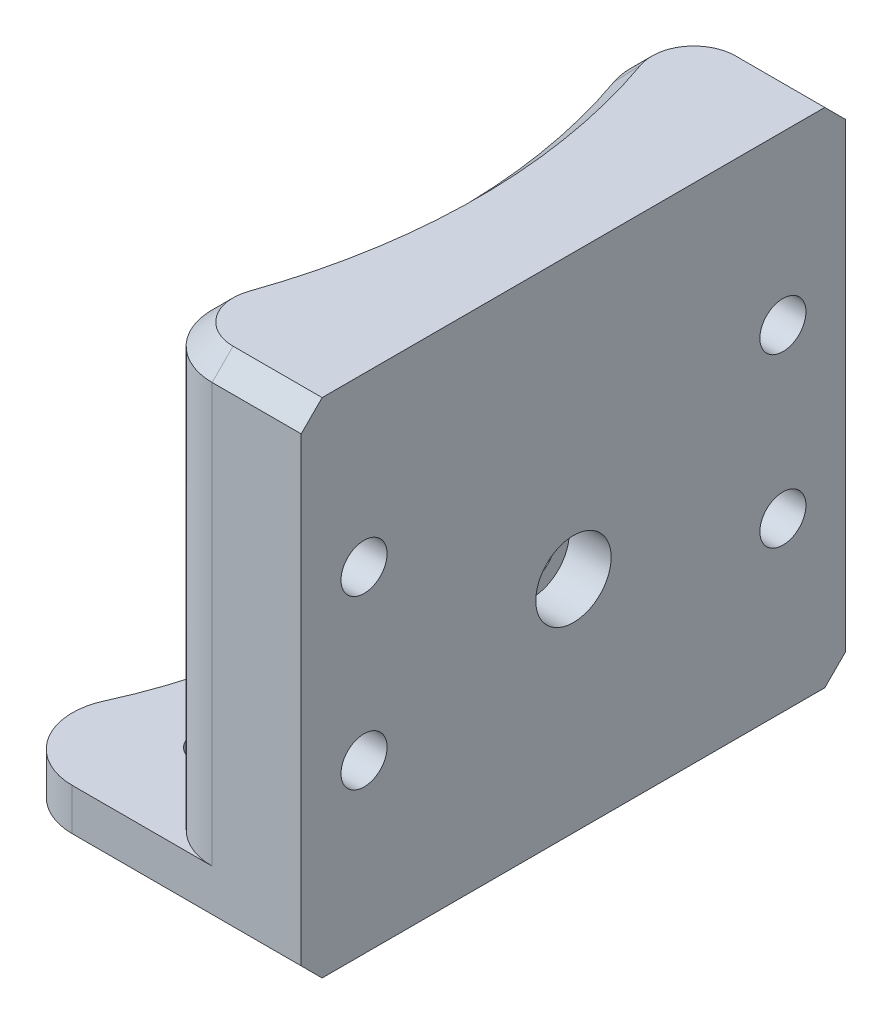
SolidWorks part; units mm, degrees
ref_plane "Спереди" through (0, 0, 0) normal (0, 0, 1) x (1, 0, 0)
ref_plane "Сверху" through (0, 0, 0) normal (0, 1, 0) x (1, 0, 0)
ref_plane "Справа" through (0, 0, 0) normal (1, 0, 0) x (0, 0, -1)
sketch "Эскиз1" plane through (0, 0, 0) normal (0, 1, 0) x (1, 0, 0)
  line L0 (23.6854, 8) -> (23.6854, -8) construction
  line L1 (16.4924, 13) -> (32.75, 13)
  line L2 (16.4924, 13) -> (16.4924, -13) construction
  line L3 (16.4924, -13) -> (32.75, -13)
  line L4 (32.75, 13) -> (32.75, -13)
  circle A0 centre (0, 0) radius 25 construction
  circle A2 centre (0, 0) radius 21
  circle A3 centre (23.6854, 8) radius 1.1
  circle A4 centre (23.6854, -8) radius 1.1
  dimension "D1" = 50
  dimension "D6" = 2.2
  dimension "D7" = 2.2
  dimension "D3" = 26
  dimension "D4" = 32.75
  dimension "D5" = 16
extrude "Бобышка-Вытянуть1" add sketch "Эскиз1" along normal blind 24 contours A2 L3 L4 L1 A4 A3 region at (26.1479, 0, 0)
sketch "Эскиз2" plane through (0, 24, 0) normal (0, 1, 0) x (1, 0, 0)
  circle A0 centre (0, 0) radius 25 construction
  circle A1 centre (0, 0) radius 27.2
  dimension "D1" = 2.2
extrude "Вырез-Вытянуть1" cut sketch "Эскиз2" against normal offset from surface (21 mm away) 3 up to face at (23.6854, 0, 9.1)
fillet "Скругление1" radius 3 4 edges at (23.8923, 13.5, 13) (23.8923, 13.5, -13) (16.4924, 1.5, -13) (16.4924, 1.5, 13)
sketch "Эскиз3" plane through (32.75, 0, 0) normal (1, 0, 0) x (0, 0, -1)
  line L0 (13, 0) -> (-13, 0) construction
  line L1 (-13, 12) -> (13, 12) construction
  line L2 (-10, 16) -> (-10, 8) construction
  line L3 (0, 0) -> (0, 24) construction
  line L4 (13, 24) -> (-13, 24) construction
  line L5 (-13, 24) -> (-13, 0) construction
  line L6 (13, 24) -> (13, 0) construction
  circle A0 centre (0, 10.5) radius 1.1
  circle A2 centre (-10, 16) radius 1.1
  circle A3 centre (-10, 8) radius 1.1
  circle A4 centre (10, 8) radius 1.1
  circle A5 centre (10, 16) radius 1.1
  point P4 (0, 0)
  point P17 (-13, 12)
  dimension "D1" = 2.2
  dimension "D3" = 2.2
  dimension "D2" = 10.5
  dimension "D4" = 8
  dimension "D5" = 20
extrude "Вырез-Вытянуть2" cut sketch "Эскиз3" against normal through all
chamfer "Фаска2" distance 1 angle 45 10 edges at (30.6232, 24, -13) (26.0489, 24, -11.7349) (27.2, 24, 0) (30.6232, 24, 13) (26.0489, 24, 11.7349) (27.2837, 0, -13) (19.2925, 0, -11.6202) (21, 0, 0) (19.2925, 0, 11.6202) (27.2837, 0, 13)
sketch "Эскиз4" plane through (0, 0, 0) normal (1, 0, 0) x (0, 0, -1)
  line L0 (-13, 12) -> (13, 12) construction
  line L1 (-8, 14.8453) -> (-8, 17.1547)
  line L2 (-8, 17.1547) -> (-10, 18.3094)
  line L3 (-10, 18.3094) -> (-12, 17.1547)
  line L4 (-12, 17.1547) -> (-12, 14.8453)
  line L5 (-12, 14.8453) -> (-10, 13.6906)
  line L6 (-10, 13.6906) -> (-8, 14.8453)
  line L7 (-13, 23) -> (-13, 1) construction
  line L8 (13, 23) -> (13, 1) construction
  line L9 (0, 24) -> (0, 0) construction
  line L10 (12, 24) -> (-12, 24) construction
  line L11 (12, 0) -> (-12, 0) construction
  line L12 (-10, 10.3094) -> (-8, 9.1547)
  line L13 (-12, 9.1547) -> (-10, 10.3094)
  line L14 (-12, 6.8453) -> (-12, 9.1547)
  line L15 (-10, 5.6906) -> (-12, 6.8453)
  line L16 (-8, 6.8453) -> (-10, 5.6906)
  line L17 (-8, 9.1547) -> (-8, 6.8453)
  line L18 (8, 9.1547) -> (8, 6.8453)
  line L19 (8, 6.8453) -> (10, 5.6906)
  line L20 (10, 5.6906) -> (12, 6.8453)
  line L21 (12, 6.8453) -> (12, 9.1547)
  line L22 (12, 9.1547) -> (10, 10.3094)
  line L23 (10, 10.3094) -> (8, 9.1547)
  line L24 (10, 13.6906) -> (8, 14.8453)
  line L25 (12, 14.8453) -> (10, 13.6906)
  line L26 (12, 17.1547) -> (12, 14.8453)
  line L27 (10, 18.3094) -> (12, 17.1547)
  line L28 (8, 17.1547) -> (10, 18.3094)
  line L29 (8, 14.8453) -> (8, 17.1547)
  circle A0 centre (-10, 16) radius 2 construction
  dimension "D1" = 4
extrude "Вырез-Вытянуть3" cut sketch "Эскиз4" along normal offset from surface (29.75 mm away) 3 up to face at (32.75, 16, -8.9)
sketch "Эскиз5" plane through (32.75, 0, 0) normal (1, 0, 0) x (0, 0, -1)
  circle A0 centre (0, 10.5) radius 1.8
  dimension "D1" = 3.6
extrude "Вырез-Вытянуть4" cut sketch "Эскиз5" against normal blind 2
sketch "Эскиз6" plane through (0, 0, 0) normal (0, -1, 0) x (1, 0, 0)
  circle A0 centre (23.6854, 8) radius 1.8
  circle A1 centre (23.6854, -8) radius 1.8
  dimension "D1" = 3.6
  dimension "D2" = 3.6
extrude "Вырез-Вытянуть5" cut sketch "Эскиз6" against normal blind 1
equation "\"motor_diameter\"= 30"
equation "\"mm_diameter\"= IIF ( \"motor_diameter\" < 34 , 41 , \"motor_diameter\" + 8 )"
equation "\"upper_shafts_diameter\"= 5"
equation "\"upper_shats_length\"= 180"
equation "\"upper_bearing_d1\"= 10"
equation "\"upper_bearing_d2\"= 5"
equation "\"upper_bearing_h\"= 15"
equation "\"lower_shafts_diameter\"= 5"
equation "\"lower_shafts_length\"= 180"
equation "\"lower_bearing_d1\"= 10"
equation "\"lower_bearing_d2\"= 5"
equation "\"lower_bearing_h\"= 15"
equation "\"print_offset\"= 0.2"
equation "\"bh_screws_d\"= 2"
equation "\"bh_screws_h\"= 20"
equation "\"bh_screws_hh_d\"= 3.4"
equation "\"bh_screws_hh_h\"= 2"
equation "\"bh_nut_d\"= 3.8"
equation "\"bh_nut_h\"= 2"
equation "\"motor_screws_d\"= 3"
equation "\"motor_screws_h\"= 16"
equation "\"motor_screws_hh_d\"= 5.5"
equation "\"motor_screws_hh_h\"= 3"
equation "\"plate_hole_distance\"= 25.4"
equation "\"plate_screws_d\"= 6.5"
equation "\"shafts_diameter\"= IIF ( \"mm_diameter\" < 42 , 42 + 8 , \"mm_diameter\" + 8 )"
equation "\"central_hole_diameter\"= 8"
equation "\"bh_thikness\"= 4"
equation "\"ends_screws_d\"= 4"
equation "\"ends_screws_h\"= 16"
equation "\"ends_screws_hh_d\"= 6.7"
equation "\"ends_screws_hh_h\"= 4.1"
equation "\"ends_nut_d\"= 6.8"
equation "\"ends_nut_h\"= 3"
equation "\"system_radius\" = ( \"shafts_diameter\" + 12 + \"bh_thikness\" / 2 ) / 2"
equation "\"encoder_distance\"= \"system_radius\" + 4"
equation "\"tape_position\"= \"encoder_distance\" - 2 + 3.9 + 1.7 / 2"
equation "\"D1@Эскиз1\"=\"shafts_diameter\""
equation "\"D2@Эскиз1\"=\"bh_thikness\""
equation "\"D4@Эскиз1\"=\"tape_position\"-6"
equation "\"D6@Эскиз1\"=\"bh_screws_d\"+\"print_offset\""
equation "\"D7@Эскиз1\"=\"D6@Эскиз1\""
equation "\"D1@Бобышка-Вытянуть1\"=\"upper_bearing_h\"+6+3"
equation "\"D1@Эскиз2\"=\"bh_thikness\"/2+\"print_offset\""
equation "\"D1@Эскиз3\"=\"bh_screws_d\"+\"print_offset\""
equation "\"D2@Эскиз3\"=\"upper_bearing_h\"/2+3"
equation "\"D3@Эскиз3\"=\"bh_screws_d\"+\"print_offset\""
equation "\"D1@Эскиз4\"=\"bh_nut_d\"+\"print_offset\""
equation "\"D1@Вырез-Вытянуть3\"=-1+12-8"
equation "\"D1@Эскиз5\"=\"bh_screws_hh_d\"+\"print_offset\""
equation "\"D1@Вырез-Вытянуть4\"=\"bh_screws_hh_h\""
equation "\"D1@Эскиз6\"=\"bh_screws_hh_d\"+\"print_offset\""
equation "\"D2@Эскиз6\"=\"D1@Эскиз6\""
equation "\"ft_sensor_d1\" = 9.8"
equation "\"ft_sensor_d2\"= 24.9"
equation "\"ft_sensor_h\"= 7"
equation "\"carbon_pipe_d\"= 14"
